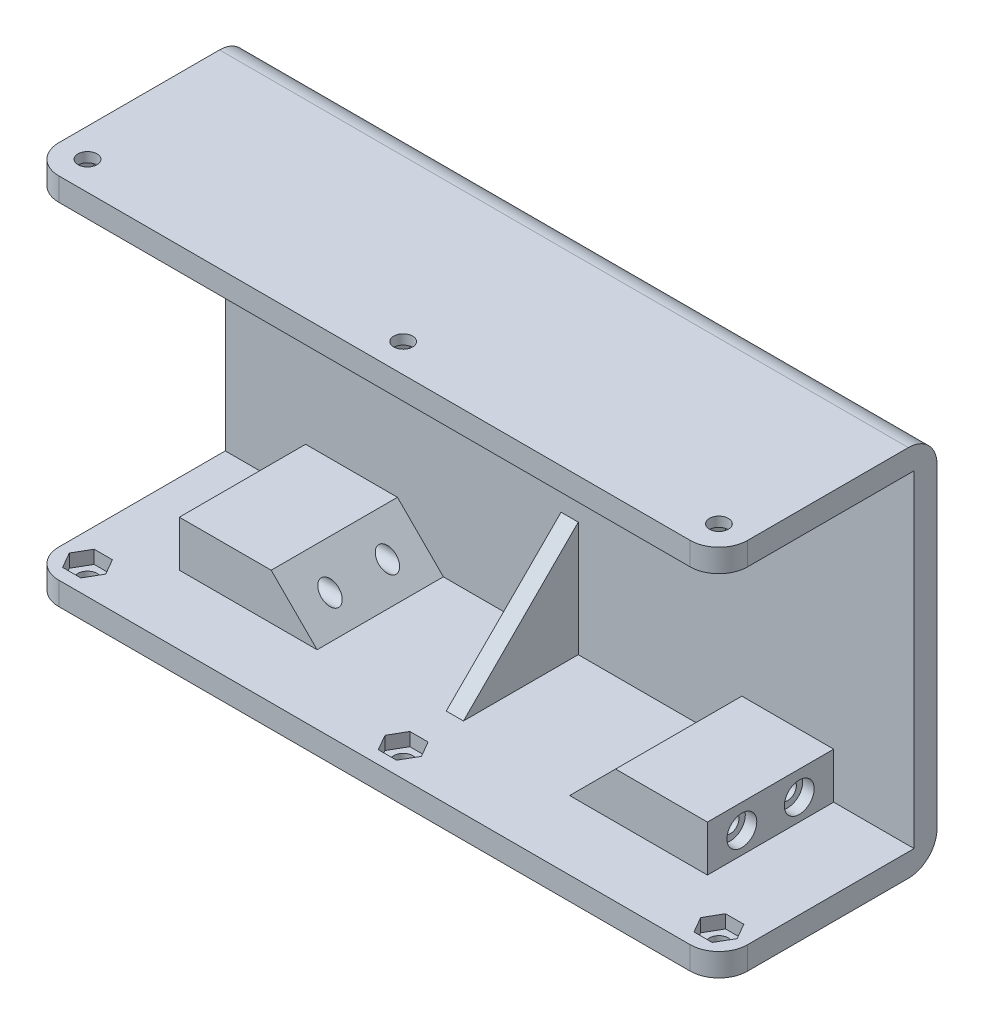
SolidWorks part; units mm, degrees
ref_plane "Front Plane" through (0, 0, 0) normal (0, 0, 1) x (1, 0, 0)
ref_plane "Top Plane" through (0, 0, 0) normal (0, 1, 0) x (1, 0, 0)
ref_plane "Right Plane" through (0, 0, 0) normal (1, 0, 0) x (0, 0, -1)
sketch "Sketch2" plane through (0, 0, 0) normal (0, 0, 1) x (1, 0, 0)
  line L1 (0, 0) -> (120, 0)
  line L2 (0, 0) -> (0, 65)
  line L3 (0, 65) -> (120, 65)
  line L4 (120, 0) -> (120, 65)
  dimension "D1" = 120
  dimension "D2" = 65
extrude "Boss-Extrude1" add sketch "Sketch2" along normal blind 38
sketch "Sketch3" plane through (0, 0, 38) normal (0, 0, 1) x (1, 0, 0)
  line L0 (106, 53) -> (106, 61)
  line L1 (92, 53) -> (106, 53)
  line L3 (92, 12) -> (106, 12)
  line L4 (106, 53) -> (106, 12)
  line L5 (106, 61) -> (120, 61)
  line L6 (120, 0) -> (120, 65) construction
  line L7 (106, 12) -> (106, 4)
  line L8 (106, 4) -> (120, 4)
  line L9 (120, 61) -> (120, 4)
  line L10 (120, 0) -> (120, 65)
  line L11 (60, 65) -> (60, 0) construction
  line L12 (120, 65) -> (0, 65) construction
  line L13 (0, 61) -> (0, 4)
  line L14 (14, 4) -> (0, 4)
  line L15 (14, 12) -> (14, 4)
  line L16 (14, 61) -> (0, 61)
  line L17 (14, 53) -> (14, 12)
  line L18 (28, 12) -> (14, 12)
  line L19 (28, 12) -> (28, 4)
  line L20 (28, 53) -> (14, 53)
  line L21 (14, 53) -> (14, 61)
  line L22 (28, 4) -> (92, 4)
  line L24 (28, 53) -> (28, 61)
  line L25 (28, 61) -> (92, 61)
  line L26 (92, 61) -> (92, 53)
  line L27 (92, 4) -> (92, 12)
  point P9 (120, 32.5)
  point P11 (120, 32.5)
  line M9 (0, 65) -> (0, 0)
  line M11 (120, 0) -> (120, 65)
  dimension "D1" = 41
  dimension "D2" = 14
  dimension "D3" = 8
  dimension "D4" = 14
extrude "Cut-Extrude1" cut sketch "Sketch3" against normal offset from surface (34 mm away) 4 contours L17 L21 L16 L14 L15 M9 | L11 L25 L24 L20 L17 L18 L19 L22 | L25 L11 L22 L27 L3 L4 L1 L26 | L7 L8 L5 L0 L4 M11 up to face at (60, 32.5, 0)
fillet "Fillet1" radius 5 2 edges at (60, 0, 0) (60, 65, 0)
sketch "Sketch4" plane through (0, 0, 38) normal (0, 0, 1) x (1, 0, 0)
  line L1 (0, 61) -> (120, 61)
  line L2 (0, 61) -> (0, 4)
  line L3 (0, 4) -> (120, 4)
  line L4 (120, 61) -> (120, 4)
extrude "Cut-Extrude2" cut sketch "Sketch4" against normal offset from surface (12 mm away) 22 up to face at (60, 32.5, 4)
fillet "Fillet2" radius 5 4 edges at (0, 2, 38) (120, 2, 38) (120, 63, 38) (0, 63, 38)
chamfer "Chamfer1" distance 10 angle 45 4 edges at (92, 4, 15) (92, 61, 15) (28, 61, 15) (28, 4, 15)
ref_plane "Plane1" through (60, 0, 0) normal (-1, 0, 0) x (0, 0, 1)
sketch "Sketch8" plane through (0, 61, 0) normal (0, -1, 0) x (1, 0, 0)
  line L0 (5, 33) -> (115, 33) construction
  line L9 (8.1754, 33) -> (6.5877, 35.75)
  line L10 (6.5877, 35.75) -> (3.4123, 35.75)
  line L11 (3.4123, 35.75) -> (1.8246, 33)
  line L12 (1.8246, 33) -> (3.4123, 30.25)
  line L13 (3.4123, 30.25) -> (6.5877, 30.25)
  line L14 (6.5877, 30.25) -> (8.1754, 33)
  line L15 (118.1754, 33) -> (116.5877, 35.75)
  line L16 (116.5877, 35.75) -> (113.4123, 35.75)
  line L17 (113.4123, 35.75) -> (111.8246, 33)
  line L18 (111.8246, 33) -> (113.4123, 30.25)
  line L19 (113.4123, 30.25) -> (116.5877, 30.25)
  line L20 (116.5877, 30.25) -> (118.1754, 33)
  line L21 (63.1754, 33) -> (61.5877, 35.75)
  line L22 (61.5877, 35.75) -> (58.4123, 35.75)
  line L23 (58.4123, 35.75) -> (56.8246, 33)
  line L24 (56.8246, 33) -> (58.4123, 30.25)
  line L25 (58.4123, 30.25) -> (61.5877, 30.25)
  line L26 (61.5877, 30.25) -> (63.1754, 33)
  circle A0 centre (5, 33) radius 2.75 construction
  circle A1 centre (115, 33) radius 2.75 construction
  circle A2 centre (60, 33) radius 2.75 construction
  circle A3 centre (5, 33) radius 1.65
  circle A4 centre (60, 33) radius 1.65
  circle A5 centre (115, 33) radius 1.65
  point P20 (5, 30.25)
  dimension "D4" = 3.3
  dimension "D1" = 5.5
  dimension "D2" = 5.5
  dimension "D3" = 5.5
extrude "Cut-Extrude4" cut sketch "Sketch8<2>" against normal through all contours A3 | A4 | A5 region at (5, 61, 33) region at (60, 61, 33) region at (115, 61, 33)
sketch "Sketch8<2>" plane through (0, 61, 0) normal (0, -1, 0) x (1, 0, 0) same geometry as "Sketch8"
extrude "Cut-Extrude3" cut sketch "Sketch8" against normal blind 2.3
ref_plane "Plane2" through (0, 32.5, 0) normal (0, 1, 0) x (1, 0, 0)
mirror "Mirror1" about plane through (0, 32.5, 0) normal (0, 1, 0) of "Cut-Extrude4", "Cut-Extrude3"
sketch "Sketch10" plane through (106, 0, 0) normal (1, 0, 0) x (0, 0, -1)
  line L0 (-15, 57.25) -> (-15, 7.75) construction
  line L1 (-15, 12) -> (-15, 53) construction
  line L2 (-4, 12) -> (-26, 12) construction
  line L3 (-4, 53) -> (-26, 53) construction
  line L5 (-20, 57.25) -> (-10, 57.25) construction
  line L6 (-20, 7.75) -> (-10, 7.75) construction
  circle A0 centre (-20, 57.25) radius 1.5
  circle A1 centre (-10, 57.25) radius 1.5
  circle A2 centre (-10, 7.75) radius 1.5
  circle A3 centre (-20, 7.75) radius 1.5
  point P8 (-15, 57.25)
  point P11 (-15, 32.5)
  point P12 (-15, 32.5)
  point P15 (-15, 7.75)
  dimension "D4" = 3
  dimension "D1" = 49.5
  dimension "D2" = 10
  dimension "D3" = 10
extrude "Cut-Extrude5" cut sketch "Sketch10" against normal through all
sketch "Sketch6" plane through (60, 0, 0) normal (-1, 0, 0) x (0, 0, 1)
  line L0 (4, 41) -> (24, 61)
  line L2 (4, 61) -> (33, 61) construction
  line L3 (4, 24) -> (24, 4)
  line L4 (4, 4) -> (26, 4) construction
  line L5 (4, 41) -> (4, 61)
  line L6 (4, 61) -> (24, 61)
  line L7 (4, 24) -> (4, 4)
  line L8 (4, 4) -> (24, 4)
  line L9 (4, 61) -> (4, 4) construction
  dimension "D1" = 45
  dimension "D2" = 45
  dimension "D3" = 20
  dimension "D4" = 20
extrude "Boss-Extrude2" add sketch "Sketch6" along normal blind 1.5 and the other way blind 1.5 contours L7 L8 L3 | L0 L6 L5 region at (60, 10.6667, 10.6667)
sketch "Sketch11" plane through (106, 0, 0) normal (1, 0, 0) x (0, 0, -1)
  circle A0 centre (-20, 57.25) radius 2.6
  circle A1 centre (-10, 57.25) radius 2.6
  circle A2 centre (-10, 7.75) radius 2.6
  circle A3 centre (-20, 7.75) radius 2.6
  dimension "D1" = 5.2
extrude "Cut-Extrude6" cut sketch "Sketch11" against normal blind 2
mirror "Mirror2" about plane through (60, 0, 0) normal (-1, 0, 0) of "Cut-Extrude6"
